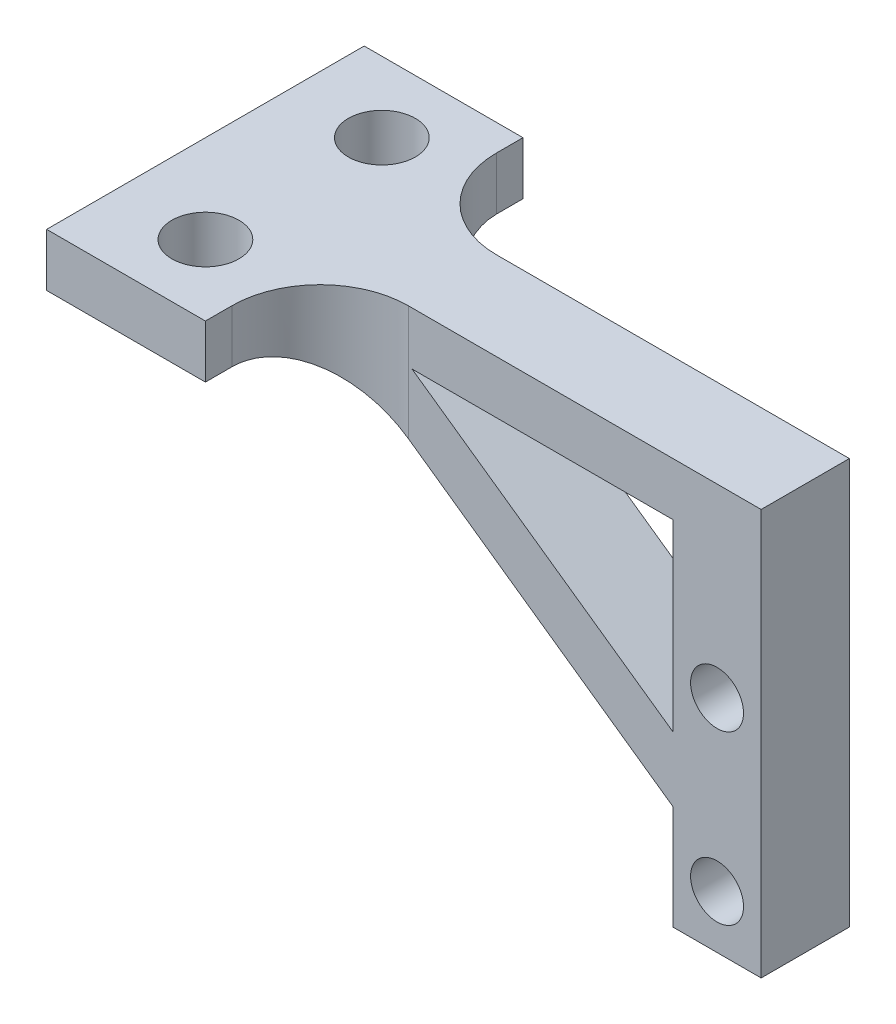
SolidWorks part; units mm, degrees
ref_plane "Front Plane" through (0, 0, 0) normal (0, 0, 1) x (1, 0, 0)
ref_plane "Top Plane" through (0, 0, 0) normal (0, 1, 0) x (1, 0, 0)
ref_plane "Right Plane" through (0, 0, 0) normal (1, 0, 0) x (0, 0, -1)
sketch "Sketch1" plane through (0, 0, 0) normal (0, 1, 0) x (1, 0, 0)
  line L0 (0, 0) -> (0, 10) construction
  line L1 (0, 5) -> (-5, 5) construction
  line L2 (-5, -4) -> (4, -4)
  line L3 (-5, -4) -> (-5, 14)
  line L4 (-5, 14) -> (4, 14)
  line L5 (4, -4) -> (4, 14)
  circle A0 centre (0, 0) radius 1.9
  circle A1 centre (0, 10) radius 1.9
  dimension "D1" = 3.8
  dimension "D2" = 10
  dimension "D3" = 5
  dimension "D4" = 4
  dimension "D5" = 18
extrude "body mount" add sketch "Sketch1" along normal blind 3
sketch "Sketch2" plane through (4, 0, 0) normal (1, 0, 0) x (0, 0, -1)
  line L0 (-4, 0) -> (14, 0) construction
  line L1 (7.5, 0) -> (2.5, 0)
  line L2 (7.5, 0) -> (7.5, 3)
  line L3 (7.5, 3) -> (2.5, 3)
  line L4 (2.5, 0) -> (2.5, 3)
  line L5 (-4, 3) -> (14, 3) construction
  line L6 (5, 3) -> (5, 0) construction
  dimension "D1" = 5
extrude "Boss-Extrude2" add sketch "Sketch2" along normal blind 25
sketch "Sketch3" plane through (0, 0, 0) normal (0, -1, 0) x (1, 0, 0)
  line L0 (29, -7.5) -> (4, -7.5) construction
  line L1 (29, -2.5) -> (24, -2.5)
  line L2 (29, -2.5) -> (29, -7.5)
  line L3 (29, -7.5) -> (24, -7.5)
  line L4 (24, -2.5) -> (24, -7.5)
  dimension "D1" = 5
extrude "Boss-Extrude3" add sketch "Sketch3" along normal blind 20
sketch "Sketch4" plane through (0, 0, -7.5) normal (0, 0, -1) x (-1, 0, 0)
  line L0 (-26.5, -20) -> (-26.5, -4.5881) construction
  line L1 (-24, -20) -> (-29, -20) construction
  circle A0 centre (-26.5, -17) radius 1.5
  circle A1 centre (-26.5, -7.5) radius 1.5
  dimension "D1" = 3
  dimension "D2" = 9.5
  dimension "D3" = 3
extrude "Cut-Extrude1" cut sketch "Sketch4" against normal blind 20
ref_plane "Plane1" through (0, 0, -5) normal (0, 0, -1) x (-1, 0, 0)
sketch "Sketch5" plane through (0, 0, -5) normal (0, 0, -1) x (-1, 0, 0)
  line L0 (-6.6052, 0) -> (-24, -12.25) construction
  line L1 (-24, -20) -> (-24, 0) construction
  line L2 (-26.5, -17) -> (-26.5, -7.5) construction
  line L3 (-26.5, -12.25) -> (-24, -12.25) construction
  line L4 (-24, -10.4154) -> (-9.2103, 0)
  line L5 (-24, 0) -> (-4, 0) construction
  line L6 (-24, -14.0846) -> (-4, 0)
  line L7 (-4, 0) -> (5, 0) construction
  line L8 (-24, -14.0846) -> (-24, -10.4154)
  line L9 (-9.2103, 0) -> (-4, 0)
  dimension "D1" = 3
extrude "Boss-Extrude4" add sketch "Sketch5" along normal up to surface and the other way up to surface up to face at (25, -7.5, -7.5) other way up to face at (25, -7.5, -2.5)
fillet "Fillet2" radius 5 2 edges
